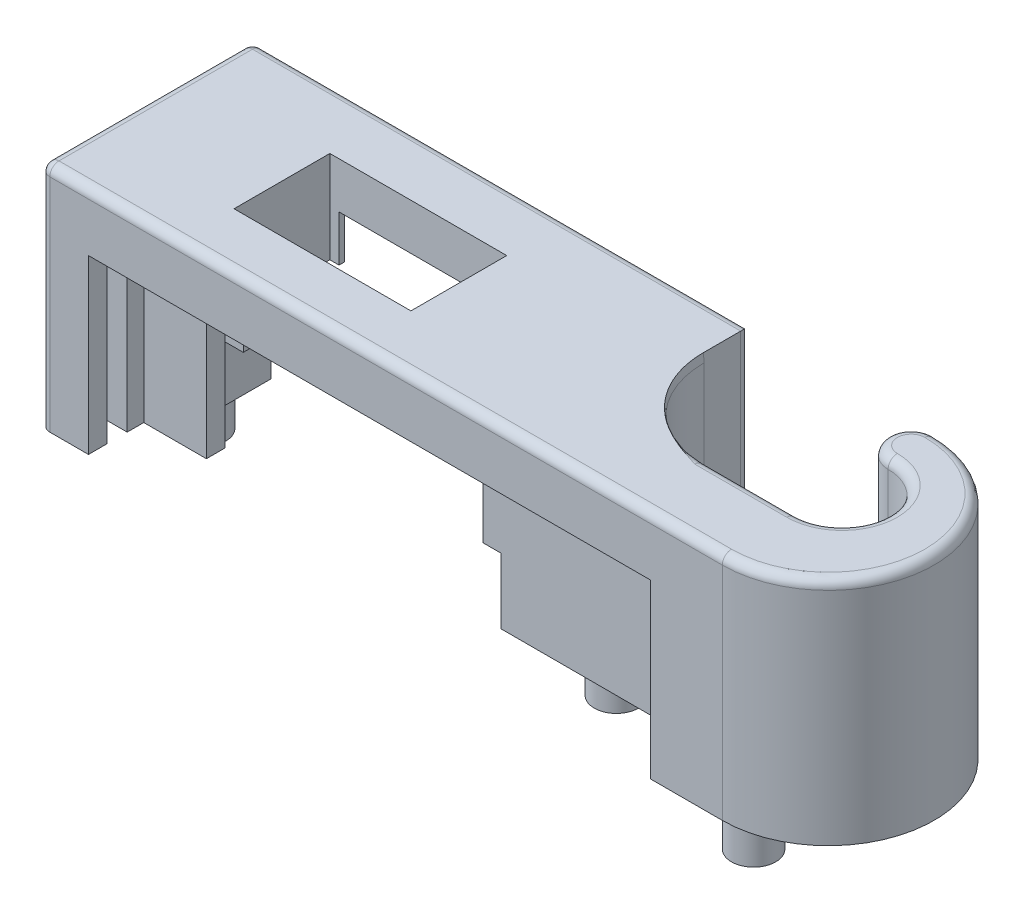
SolidWorks part; units mm, degrees
material "ABS"
ref_plane "Front Plane" through (0, 0, 0) normal (0, 0, 1) x (1, 0, 0)
ref_plane "Top Plane" through (0, 0, 0) normal (0, 1, 0) x (1, 0, 0)
ref_plane "Right Plane" through (0, 0, 0) normal (1, 0, 0) x (0, 0, -1)
sketch "Sketch1" plane through (0, 0, 0) normal (0, 1, 0) x (1, 0, 0)
  line L1 (0, 0) -> (74, 0)
  line L2 (0, 0) -> (0, 8)
  line L3 (0, 8) -> (74, 8)
  line L4 (74, 0) -> (74, 8)
  line L5 (0, 8) -> (54, 8)
  line L6 (0, 8) -> (0, 23)
  line L7 (0, 23) -> (54, 23)
  line L8 (54, 8) -> (54, 23)
  arc A0 (74, 8) -> (74, 18) centre (74, 13) ccw
  arc A1 (74, 18) -> (74, 23) centre (74, 20.5) cw
  arc A2 (74, 23) -> (74, 0) centre (74, 11.5) cw
  dimension "D1" = 74
  dimension "D2" = 8
  dimension "D3" = 15
  dimension "D4" = 54
  dimension "D5" = 10
  dimension "D6" = 5
extrude "Right Half" add sketch "Sketch1" along normal blind 25 contours L1 L4 L3 L2 | L3 L8 L7 L6 | A2 A1 A0 L4 region at (37, 0, -4) region at (79.1612, 0, -11.6652) region at (27, 0, -15.5)
fillet "Fillet3" radius 1 10 edges at (64, 25, -8) (79, 25, -13) (71.5, 25, -20.5) (85.5, 25, -11.5) (54, 12.5, -23) (37, 25, 0) (27, 25, -23) (0, 25, -11.5) (0, 12.5, 0) (0, 12.5, -23)
fillet "Fillet1" radius 10 2 edges at (54, 12, -8) (54, 24.7071, -7.7071)
sketch "Sketch2" plane through (0, 0, 0) normal (0, -1, 0) x (1, 0, 0)
  line L0 (1, -23) -> (53, -23) construction
  line L1 (52, -23) -> (2, -23)
  line L2 (52, -23) -> (52, -21)
  line L3 (52, -21) -> (2, -21)
  line L4 (2, -23) -> (2, -21)
  line L5 (0, -1) -> (0, -22) construction
  line L6 (49.8, -21) -> (4.2, -21)
  line L7 (49.8, -21) -> (49.8, -19)
  line L8 (49.8, -19) -> (4.2, -19)
  line L9 (4.2, -21) -> (4.2, -19)
  line L10 (52, -19) -> (2, -19)
  line L11 (52, -19) -> (52, -17)
  line L12 (52, -17) -> (2, -17)
  line L13 (2, -19) -> (2, -17)
  dimension "D1" = 2
  dimension "D2" = 2
  dimension "D3" = 2.2
  dimension "D4" = 2.2
  dimension "D5" = 2
  dimension "D6" = 2.2
  dimension "D7" = 2.2
  dimension "D8" = 50
  dimension "D9" = 2
  dimension "D10" = 2
extrude "Cut-Extrude2" cut sketch "Sketch2" against normal blind 22.7 contours L13 L10 L8 L11 L12 | L3 L4 L1 L2 region at (27, 0, -18)
extrude "Cut-Extrude3" cut sketch "Sketch2<4>" against normal blind 20.5 contours L9 L3 L7 L8 region at (27, 0, -20)
sketch "Sketch2<4>" plane through (0, 0, 0) normal (0, -1, 0) x (1, 0, 0) same geometry as "Sketch2"
sketch "Sketch3" plane through (0, 0, 0) normal (0, -1, 0) x (1, 0, 0)
  line L1 (64, -8) -> (74, -8) construction
  line L2 (42, -10) -> (12, -10)
  line L3 (42, -10) -> (12, -10)
  line L4 (42, -10) -> (42, -12)
  line L6 (44, -10) -> (10, -10)
  line L7 (44, -10) -> (44, -8)
  line L8 (44, -8) -> (10, -8)
  line L9 (10, -10) -> (10, -8)
  line L10 (42, -8) -> (12, -8)
  line L11 (42, -8) -> (42, -6)
  line L12 (42, -6) -> (12, -6)
  line L13 (12, -8) -> (12, -6)
  line L19 (42, -12) -> (12, -12)
  line L20 (12, -10) -> (12, -12)
  line L21 (52, -17) -> (2, -17) construction
  line L22 (42, -12) -> (12, -12)
  line L23 (42, -12) -> (42, -17)
  line L24 (42, -17) -> (12, -17)
  line L25 (12, -12) -> (12, -17)
  line M11 (2, -17) -> (52, -17)
  dimension "D1" = 2
  dimension "D2" = 2
  dimension "D3" = 2
  dimension "D4" = 34
  dimension "D5" = 2
  dimension "D6" = 2
  dimension "D7" = 2
  dimension "D8" = 2
  dimension "D9" = 2
  dimension "D10" = 2
  dimension "D11" = 2
extrude "Cut-Extrude4" cut sketch "Sketch3" against normal blind 15 contours L13 L8 L11 L12 | L2 L20 L19 L4 | L19 L25 L23 M11 region at (27, 0, -11) region at (27, 0, -14.5) region at (27, 0, -7)
extrude "PCB rail" cut sketch "Sketch3<3>" against normal blind 17 contours L9 L6 L3 L7 L8 region at (27, 0, -9)
sketch "Sketch3<3>" plane through (0, 0, 0) normal (0, -1, 0) x (1, 0, 0) same geometry as "Sketch3"
ref_plane "Right edge of BB" through (0, 17, 0) normal (0, -1, 0) x (-1, 0, 0)
sketch "Sketch11" plane through (0, 0, -17) normal (0, 0, -1) x (-1, 0, 0)
  line L0 (-42, 15) -> (-42, 0) construction
  line L1 (-42, 9) -> (-47, 9)
  line L2 (-42, 9) -> (-42, 0)
  line L3 (-42, 0) -> (-47, 0)
  line L4 (-47, 9) -> (-47, 0)
  line L5 (-52, 0) -> (-42, 0) construction
  line L6 (-12, 15) -> (-42, 15) construction
  line L7 (-12, 15) -> (-12, 0) construction
  line L8 (-12, 8) -> (-8, 8)
  line L9 (-12, 8) -> (-12, 0)
  line L10 (-12, 0) -> (-8, 0)
  line L11 (-8, 8) -> (-8, 0)
  line L12 (-12, 0) -> (-2, 0) construction
  line L14 (-38, 15) -> (-16, 15)
  line L15 (-38, 15) -> (-38, 20)
  line L16 (-38, 20) -> (-16, 20)
  line L17 (-16, 15) -> (-16, 20)
  dimension "D1" = 5
  dimension "D2" = 6
  dimension "D3" = 4
  dimension "D4" = 7
  dimension "D5" = 5
  dimension "D6" = 4
  dimension "D7" = 4
extrude "Main Power Access" cut sketch "Sketch11" against normal blind 7
sketch "Sketch12" plane through (0, 25, 0) normal (0, 1, 0) x (1, 0, 0)
  line L0 (44, 8) -> (10, 8) construction
  line L1 (15, 16.4) -> (34.2, 16.4)
  line L2 (15, 16.4) -> (15, 6)
  line L3 (15, 6) -> (34.2, 6)
  line L4 (34.2, 16.4) -> (34.2, 6)
  line L5 (10, 10) -> (10, 8) construction
  dimension "D1" = 8.4
  dimension "D2" = 10.4
  dimension "D3" = 5
  dimension "D4" = 19.2
extrude "USB Access" cut sketch "Sketch12" against normal through all
fillet "Fillet2" radius 3 2 edges at (12, 15, -13.5) (42, 15, -13.5)
sketch "Sketch6" plane through (0, 0, 0) normal (0, -1, 0) x (1, 0, 0)
  line L0 (1, 0) -> (74, 0) construction
  line L1 (66.2, 0) -> (5.2, 0)
  line L2 (66.2, 0) -> (66.2, -2)
  line L3 (66.2, -2) -> (5.2, -2)
  line L4 (5.2, 0) -> (5.2, -2)
  line L5 (0, -1) -> (0, -22) construction
  line L6 (68.4, -2) -> (3, -2)
  line L7 (68.4, -2) -> (68.4, -4.2)
  line L8 (68.4, -4.2) -> (3, -4.2)
  line L9 (3, -2) -> (3, -4.2)
  line L10 (66.2, -4.2) -> (5.2, -4.2)
  line L11 (66.2, -4.2) -> (66.2, -6)
  line L12 (66.2, -6) -> (5.2, -6)
  line L13 (5.2, -4.2) -> (5.2, -6)
  line M11 (12, -6) -> (42, -6)
  line M23 (74, 0) -> (1, 0)
  dimension "D1" = 2
  dimension "D2" = 61
  dimension "D3" = 2.2
  dimension "D4" = 2
  dimension "D5" = 2.2
  dimension "D6" = 2.2
  dimension "D7" = 1.8
  dimension "D8" = 2.2
  dimension "D9" = 2.2
  dimension "D10" = 3
extrude "Cut-Extrude7" cut sketch "Sketch6" against normal blind 20.7 contours L6 L9 L8 L7 L3 region at (35.7, 0, -3.1)
extrude "Cut-Extrude8" cut sketch "Sketch6<3>" against normal blind 18.7 contours L8 L13 L12 L11 M11 | L4 L3 L2 M23 region at (35.7, 0, -1) region at (35.7, 0, -5.1)
sketch "Sketch6<3>" plane through (0, 0, 0) normal (0, -1, 0) x (1, 0, 0) same geometry as "Sketch6"
sketch "Sketch13" plane through (0, 0, 0) normal (0, -1, 0) x (1, 0, 0)
  line L0 (8, -10) -> (8, -17) construction
  line L1 (5.2, -4.2) -> (3, -4.2) construction
  line L2 (66.2, -6) -> (42, -6) construction
  line L3 (47, -10) -> (47, -17) construction
  line L4 (68.4, -2) -> (68.4, -4.2) construction
  line L5 (66.2, 0) -> (74, 0) construction
  circle A0 centre (51.5, -11) radius 2.4
  circle A1 centre (4, -13.7) radius 2.4
  circle A2 centre (73.4, -4) radius 2.4
  dimension "D1" = 4.8
  dimension "D2" = 4.8
  dimension "D3" = 4.8
  dimension "D4" = 4
  dimension "D5" = 9.5
  dimension "D6" = 5
  dimension "D7" = 4.5
  dimension "D8" = 5
  dimension "D9" = 4
extrude "Boss-Extrude4" add sketch "Sketch13" along normal blind 5
sketch "Sketch14" plane through (0, -5, 0) normal (0, -1, 0) x (1, 0, 0)
  circle A0 centre (73.4, -4) radius 1.1
  circle A1 centre (51.5, -11) radius 1.1
  circle A2 centre (4, -13.7) radius 1.1
  dimension "D1" = 2.2
  dimension "D2" = 2.2
  dimension "D3" = 2.2
extrude "Cut-Extrude11" cut sketch "Sketch14" against normal blind 12.7
sketch "Sketch15" plane through (0, 0, -6) normal (0, 0, 1) x (1, 0, 0)
  line L0 (42, 15) -> (34.2, 15) construction
  line L1 (42, 0) -> (44, 0)
  line L2 (42, 0) -> (42, 7.112)
  line L3 (42, 7.112) -> (44, 7.112)
  line L4 (44, 0) -> (44, 7.112)
  line L5 (35.777, 15) -> (29.681, 15)
  line L6 (35.777, 15) -> (35.777, 17)
  line L7 (35.777, 17) -> (29.681, 17)
  line L8 (29.681, 15) -> (29.681, 17)
  line L9 (42, 15) -> (42, 0) construction
  dimension "D1" = 2
  dimension "D2" = 7.112
  dimension "D3" = 2
  dimension "D4" = 6.096
  dimension "D5" = 6.223
extrude "Cut-Extrude12" cut sketch "Sketch15" against normal blind 8
